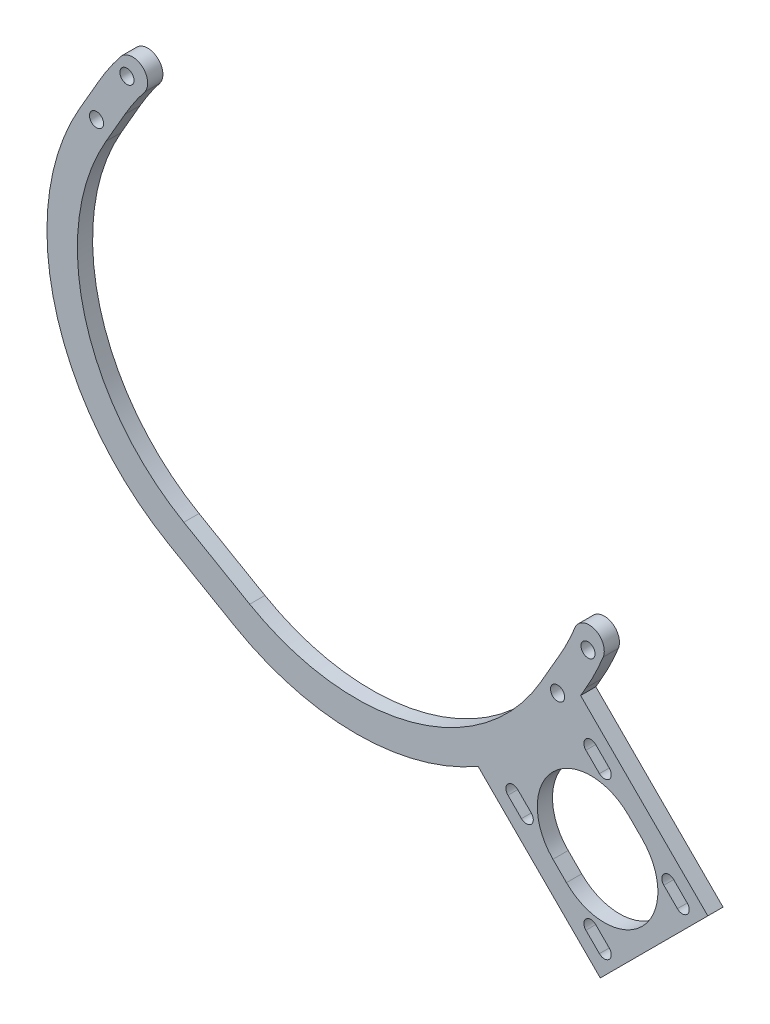
SolidWorks part; units mm, degrees
ref_plane "Front Plane" through (0, 0, 0) normal (0, 0, 1) x (1, 0, 0)
ref_plane "Top Plane" through (0, 0, 0) normal (0, 1, 0) x (1, 0, 0)
ref_plane "Right Plane" through (0, 0, 0) normal (1, 0, 0) x (0, 0, -1)
sketch "Sketch1" plane through (0, 0, -14.157) normal (0, 0, -1) x (-1, 0, 0)
  line L0 (-49.1723, -34.5021) -> (-53.1411, -27.628)
  line L1 (-2.2729, 1.7407) -> (29.3872, -53.0962) construction
  line L2 (20.2218, -53.0962) -> (27.0959, -49.1274)
  line L3 (33.9699, -45.1587) -> (20.2218, -53.0962) construction
  line L4 (17.0468, -47.5969) -> (23.9209, -43.6282)
  line L5 (-43.6731, -31.3271) -> (-47.6418, -24.453)
  line L6 (47.0648, 21.0604) -> (43.096, 27.9345)
  line L7 (30.7949, -39.6594) -> (23.9209, -43.6282)
  line L8 (33.9699, -45.1587) -> (27.0959, -49.1274)
  line L9 (52.564, 24.2354) -> (48.5953, 31.1095)
  arc A0 (-53.1411, -27.628) -> (-56.7299, -20.2712) centre (-2.2729, 1.7407) cw
  arc A3 (-61.0104, 1.7407) -> (-53.1411, -27.628) centre (-2.2729, 1.7407) ccw construction
  circle A4 centre (-53.5664, -20.5413) radius 1.1303 construction
  arc A5 (-49.1723, -34.5021) -> (20.2218, -53.0962) centre (-5.1782, -9.1021) ccw
  arc A6 (-43.6731, -31.3271) -> (17.0468, -47.5969) centre (-5.1782, -9.1021) ccw
  arc A7 (-47.6418, -24.453) -> (-50.8427, -17.8916) centre (-2.2729, 1.7407) cw
  arc A8 (-56.7299, -20.2712) -> (-50.8427, -17.8916) centre (-53.7863, -19.0814) cw
  arc A9 (44.0185, 37.8959) -> (39.014, 33.9872) centre (41.5163, 35.9416) ccw
  arc A10 (43.096, 27.9345) -> (39.014, 33.9872) centre (-2.2729, 1.7407) ccw
  arc A11 (47.0648, 21.0604) -> (30.7949, -39.6594) centre (8.5699, -1.1646) cw
  arc A12 (52.564, 24.2354) -> (33.9699, -45.1587) centre (8.5699, -1.1646) cw
  arc A13 (48.5953, 31.1095) -> (44.0185, 37.8959) centre (-2.2729, 1.7407) ccw
  dimension "D1" = 3.175
  dimension "D2" = 6.35
extrude "Boss-Extrude1" add sketch "Sketch1" along normal blind 3.175
ref_plane "Plane1" through (0, -58.42, 0) normal (0, 1, 0) x (-1, 0, 0)
ref_plane "Plane2" through (0, 0, -14.157) normal (0, 0, 1) x (1, 0, 0)
ref_axis "Axis2" through (-66.4483, 0, -14.157) along (1, 0, 0)
ref_axis "Axis3" through (0, 0, -25.4783) along (0, 0, 1)
ref_point "Point1"
ref_axis "Axis4" through (0, -70.9509, -14.157) along (0, 1, 0)
sketch "Sketch6" plane through (0, 0, -14.157) normal (0, 0, 1) x (1, 0, 0)
  line L0 (0, 0) -> (52.9615, -52.9615) construction
  line L1 (0, -70.9509) -> (0, 0.8498) construction
  line L10 (78.5772, -56.1266) -> (56.1266, -78.5772)
  line L15 (78.5772, -56.1266) -> (49.7964, -27.3457)
  line L16 (56.1266, -78.5772) -> (27.3457, -49.7964)
  line L17 (49.7964, -27.3457) -> (27.3457, -49.7964)
  line L18 (78.5772, -56.1266) -> (27.3457, -49.7964) construction
  line L19 (56.1266, -78.5772) -> (49.7964, -27.3457) construction
  line L20 (54.1509, -54.1509) -> (56.9707, -56.9707) construction
  line L21 (62.0536, -46.2483) -> (64.8734, -49.0681)
  line L22 (46.2483, -62.0536) -> (49.0681, -64.8734)
  line L23 (36.6517, -52.924) -> (60.8753, -77.1475) construction
  line L24 (56.9707, -73.243) -> (54.1509, -70.4232) construction
  line L25 (76.7104, -60.4382) -> (52.1055, -35.8333) construction
  line L26 (55.947, -74.2667) -> (53.1272, -71.4469)
  line L27 (57.9945, -72.2192) -> (55.1747, -69.3994)
  line L28 (37.8787, -54.1509) -> (40.6985, -56.9707) construction
  line L29 (38.9025, -53.1272) -> (41.7223, -55.947)
  line L30 (36.855, -55.1747) -> (39.6748, -57.9945)
  line L31 (54.1509, -37.8787) -> (56.9707, -40.6985) construction
  line L32 (55.1747, -36.855) -> (57.9945, -39.6748)
  line L33 (53.1272, -38.9025) -> (55.947, -41.7223)
  line L34 (70.4232, -54.1509) -> (73.243, -56.9707) construction
  line L35 (71.4469, -53.1272) -> (74.2667, -55.947)
  line L36 (69.3994, -55.1747) -> (72.2192, -57.9945)
  line L37 (40.6985, -56.9707) -> (56.9707, -40.6985) construction
  arc A0 (55.947, -74.2667) -> (57.9945, -72.2192) centre (56.9707, -73.243) ccw
  arc A1 (55.1747, -69.3994) -> (53.1272, -71.4469) centre (54.1509, -70.4232) ccw
  arc A2 (-17.0468, -47.5969) -> (43.6731, -31.3271) centre (5.1782, -9.1021) ccw construction
  arc A3 (62.0536, -46.2483) -> (46.2483, -62.0536) centre (54.1509, -54.1509) ccw
  arc A4 (49.0681, -64.8734) -> (64.8734, -49.0681) centre (56.9707, -56.9707) ccw
  arc A5 (38.9025, -53.1272) -> (36.855, -55.1747) centre (37.8787, -54.1509) ccw
  arc A6 (39.6748, -57.9945) -> (41.7223, -55.947) centre (40.6985, -56.9707) ccw
  arc A7 (55.1747, -36.855) -> (53.1272, -38.9025) centre (54.1509, -37.8787) ccw
  arc A8 (55.947, -41.7223) -> (57.9945, -39.6748) centre (56.9707, -40.6985) ccw
  arc A9 (71.4469, -53.1272) -> (69.3994, -55.1747) centre (70.4232, -54.1509) ccw
  arc A10 (72.2192, -57.9945) -> (74.2667, -55.947) centre (73.243, -56.9707) ccw
  point P3 (55.5608, -55.5608)
  point P25 (55.5608, -71.8331)
  point P30 (39.2886, -55.5608)
  point P37 (55.5608, -39.2886)
  point P44 (71.8331, -55.5608)
  dimension "D4" = 11.176
  dimension "D5" = 11.5062
  dimension "D8" = 1.4478
  dimension "D9" = 23.0124
  dimension "D14" = 1.4478
  dimension "D15" = 1.4478
  dimension "D16" = 1.4478
  dimension "D19" = 3.9878
  dimension "D1" = 45
  dimension "D2" = 95.25
  dimension "D3" = 31.75
  dimension "D6" = 11.5062
  dimension "D7" = 3.9878
  dimension "D10" = 23.0124
  dimension "D11" = 3.9878
  dimension "D12" = 3.9878
  dimension "D13" = 3.9878
  dimension "D17" = 3.175
  dimension "D18" = 3.175
  dimension "D20" = 11.5062
extrude "Boss-Extrude2" add sketch "Sketch6" against normal up to surface (3.175 mm away) up to face at (-5.7343, -12.1282, -17.332)
hole_wizard "#4 Clearance Hole1" positions "Sketch5" profile "Sketch4" hole size "#4" standard "Ansi Inch" end condition through all
sketch "Sketch5" plane through (0, 0, -17.332) normal (0, 0, -1) x (-1, 0, 0)
  circle A1 centre (-53.5664, -20.5413) radius 1.1303 construction
  circle A2 centre (49.0206, 24.0227) radius 1.1303 construction
  point P0 (-53.5664, -20.5413)
  point P5 (-47.2164, -31.5398)
  point P8 (42.6706, 35.0212)
  point P11 (49.0206, 24.0227)
sketch "Sketch4" plane through (53.5664, -20.5413, -17.332) normal (1, 0, 0) x (0, 1, 0)
  line L0 (0, 0) -> (0, 3.175)
  line L1 (0, 3.175) -> (1.4732, 3.175)
  line L2 (1.4732, 3.175) -> (1.4732, 0)
  line L5 (1.4732, 0) -> (0, 0)
  line L11 (0, -6.35) -> (0, 107.95) construction
  dimension "Thru Hole Dia." = 2.9464
  dimension "Thru Hole Depth" = 3.175
